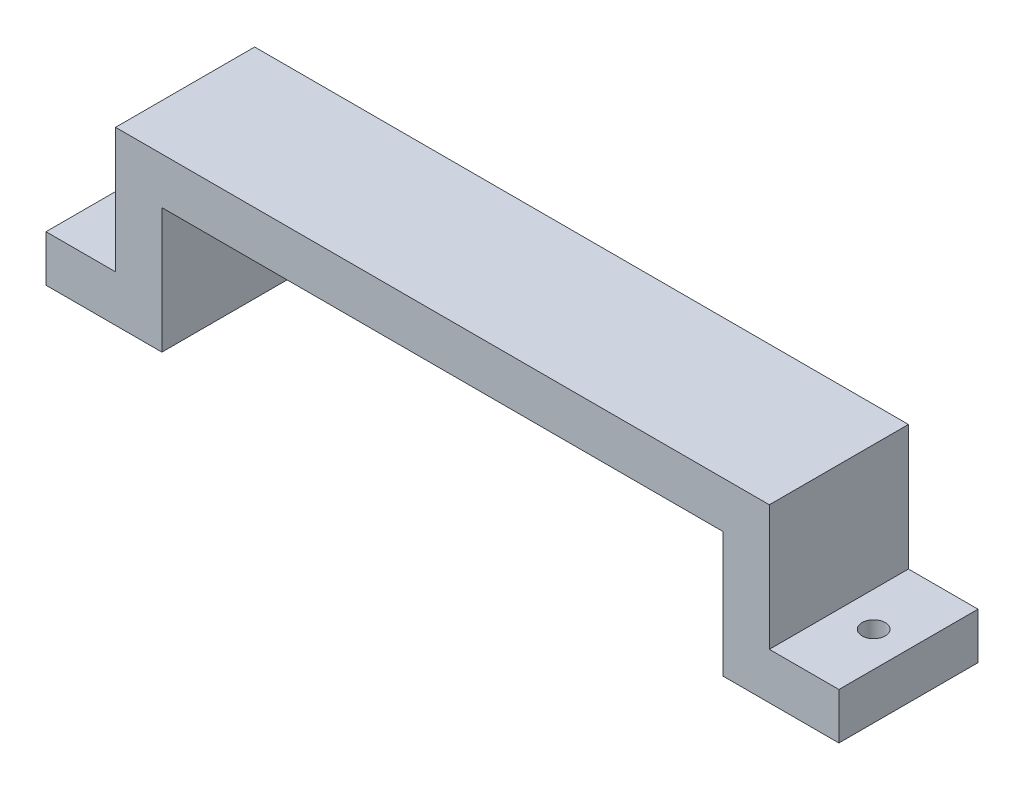
SolidWorks part; units mm, degrees
ref_plane "Front Plane" through (0, 0, 0) normal (0, 0, 1) x (1, 0, 0)
ref_plane "Top Plane" through (0, 0, 0) normal (0, 1, 0) x (1, 0, 0)
ref_plane "Right Plane" through (0, 0, 0) normal (1, 0, 0) x (0, 0, -1)
sketch "Sketch2" plane through (0, 0, 0) normal (0, 0, 1) x (1, 0, 0)
  line L1 (55, 0) -> (-55, 0) construction
  line L2 (-60.5, 0) -> (-60.5, 27)
  line L4 (0, -55) -> (0, 55) construction
  line L11 (-60.5, 0) -> (-85.5, 0)
  line L12 (-85.5, 0) -> (-85.5, 10)
  line L13 (-85.5, 10) -> (-70.5, 10)
  line L14 (-70.5, 10) -> (-70.5, 37)
  line L15 (-70.5, 37) -> (0, 37)
  line L16 (0, 37) -> (0, 27)
  line L17 (0, 27) -> (-60.5, 27)
  dimension "D1" = 60.5
  dimension "D2" = 25
  dimension "D3" = 10
  dimension "D4" = 10
  dimension "D5" = 10
  dimension "D6" = 27
extrude "Boss-Extrude1" add sketch "Sketch2" along normal blind 15 and the other way blind 15
mirror "Mirror1" about plane through (0, 0, 0) normal (1, 0, 0) of bodies 101
sketch "Sketch3" plane through (0, 10, 0) normal (0, 1, 0) x (1, 0, 0)
  line L0 (-20.35, 0) -> (20.35, 0) construction
  line L1 (-85.5, 15) -> (-85.5, -15) construction
  line L2 (0, -16.5) -> (0, 16.5) construction
  circle A0 centre (-78, 0) radius 2.5
  circle A1 centre (78, 0) radius 2.5
  dimension "D1" = 5
  dimension "D2" = 7.5
extrude "Cut-Extrude1" cut sketch "Sketch3" against normal blind 15
